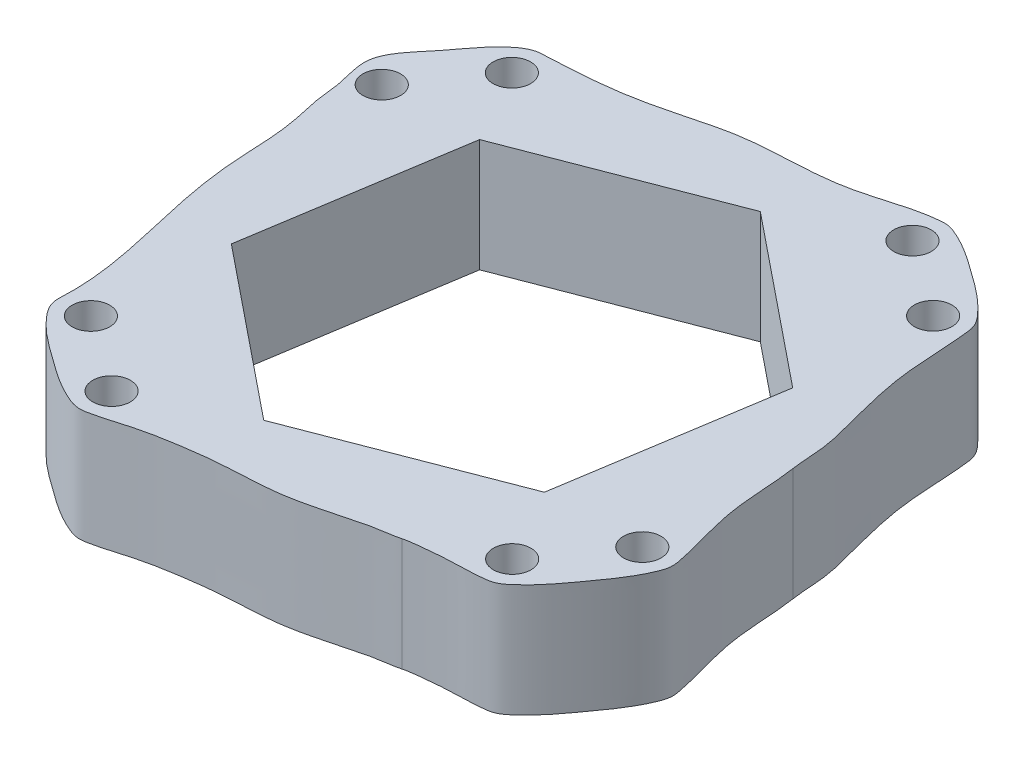
SolidWorks part; units mm, degrees
ref_plane "前视基准面" through (0, 0, 0) normal (0, 0, 1) x (1, 0, 0)
ref_plane "上视基准面" through (0, 0, 0) normal (0, 1, 0) x (1, 0, 0)
ref_plane "右视基准面" through (0, 0, 0) normal (1, 0, 0) x (0, 0, -1)
sketch "草图1" plane through (0, 0, 0) normal (0, 1, 0) x (1, 0, 0)
  circle A0 centre (0, 0) radius 17.5
  circle A1 centre (0, 0) radius 18.901
  dimension "D1" = 35
extrude "凸台-拉伸1" add sketch "草图1" along normal blind 2
sketch "草图2" plane through (0, 0, 0) normal (0, -1, 0) x (1, 0, 0)
  circle A0 centre (-10.7739, 21.1656) radius 1.5
  circle A1 centre (16.8004, 16.7872) radius 1.5
  circle A2 centre (21.1656, 10.7739) radius 1.5
  circle A3 centre (16.7872, -16.8004) radius 1.5
  circle A4 centre (10.7739, -21.1656) radius 1.5
  circle A5 centre (-16.8004, -16.7872) radius 1.5
  circle A6 centre (-21.1656, -10.7739) radius 1.5
  circle A7 centre (-16.7872, 16.8004) radius 1.5
  circle A28 centre (0, 0) radius 17.5
  spline S3 degree 3 poles (11.007, 19.7796) (11.3114, 19.6784) (14.2307, 19.3249) (16.1426, 19.3879) (17.8124, 19.1708) (19.4344, 17.903) (21.2548, 15.4236) (23.0457, 12.9332) (23.7495, 10.9887) (23.274, 8.5261) (21.9734, 4.7628) (22.0269, 1.1873) (21.7447, -0.683) knots 0 0 0 0 0.101498 0.202996 0.236379 0.269761 0.41266 0.555558 0.58894 0.622323 0.811161 1 1 1 1
  spline S4 degree 3 poles (21.7447, -0.683) (21.6068, -1.5972) (21.6068, -3.3452) (20.6875, -6.8866) (19.4907, -11.3034) (19.4854, -15.3123) (19.178, -17.8032) (17.9056, -19.4334) (15.4365, -21.2528) (12.9718, -22.9922) (11.1783, -23.6905) (8.6855, -23.5473) (4.924, -21.9674) (0.2192, -21.8124) (-3.3386, -21.5662) (-6.4463, -20.811) (-9.0785, -20.0902) (-12.7412, -19.485) (-15.1247, -19.3734) (-17.5839, -19.2481) (-19.3904, -18.0992) (-21.0258, -15.4093) (-24.0454, -12.3959) (-22.8775, -9.4491) (-22.7505, -7.0317) (-21.8371, -3.8686) (-21.9062, 0.7266) (-20.6205, 7.8807) (-19.0765, 13.1316) (-19.2816, 16.8284) knots 0 0 0 0 0.028862 0.05524 0.115062 0.172401 0.182537 0.192673 0.236063 0.279452 0.287691 0.29593 0.357119 0.414457 0.443319 0.469697 0.51526 0.529547 0.586885 0.590735 0.60701 0.6504 0.693789 0.724872 0.741288 0.770858 0.827714 0.885323 1 1 1 1
  spline S5 degree 3 poles (-19.2816, 16.8284) (-19.323, 17.5174) (-18.1907, 19.2578) (-15.4061, 21.2421) (-12.9273, 23.0421) (-10.9838, 23.7431) (-9.3566, 23.4387) (-7.2233, 22.7077) (-4.4614, 22.2162) (-1.8337, 21.8607) (0.7732, 21.7432) (3.3794, 21.5754) (7.3403, 20.5662) (8.6858, 20.19) (9.8558, 19.9936) (10.7406, 19.8682) (11.007, 19.7796) knots 0 0 0 0 0.047987 0.150696 0.253406 0.277399 0.301393 0.374345 0.447298 0.510152 0.573007 0.641327 0.709648 0.853023 0.882058 1 1 1 1
  point P24 (-22.7467, -8.1804)
  point P25 (-22.7298, -7.4478)
  point P26 (-22.1742, -4.6962)
  dimension "D1" = 3
extrude "凸台-拉伸2" add sketch "草图2" along normal blind 7 and the other way blind 2
sketch "草图3" plane through (0, 2, 0) normal (0, 1, 0) x (1, 0, 0)
  line L1 (13.4706, -10.8878) -> (16.1644, 6.222)
  line L2 (16.1644, 6.222) -> (2.6938, 17.1097)
  line L3 (2.6938, 17.1097) -> (-13.4706, 10.8878)
  line L4 (-13.4706, 10.8878) -> (-16.1644, -6.222)
  line L5 (-16.1644, -6.222) -> (-2.6938, -17.1097)
  line L6 (-2.6938, -17.1097) -> (13.4706, -10.8878)
  circle A0 centre (0, 0) radius 15 construction
  circle A2 centre (0, 0) radius 19.0235
  dimension "D1" = 30
extrude "凸台-拉伸3" add sketch "草图3" against normal up to surface (9 mm away) up to face at (4.49, -7, 11.975)
sketch "草图5" plane through (5.3884, 0, 13.9988) normal (-0.3592, 0, -0.9333) x (-0.9333, 0, 0.3592)
  line L0 (0, -7) -> (0, -3.5)
  line L1 (-8.6603, -7) -> (8.6603, -7) construction
  circle A0 centre (0, -3.5) radius 1.5
  dimension "D1" = 3
  dimension "D2" = 3.5
